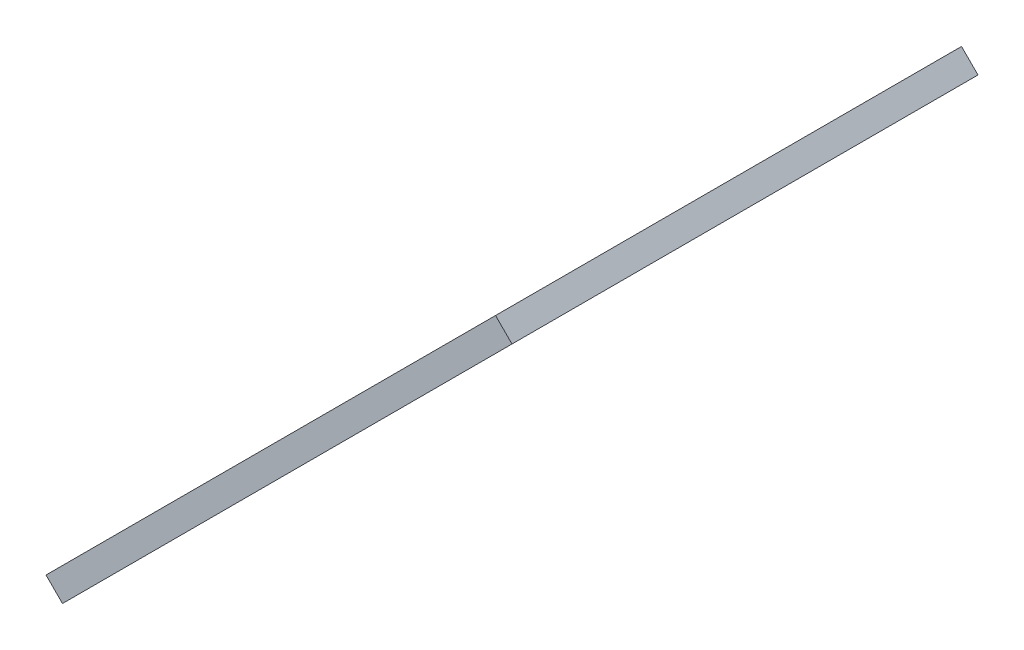
SolidWorks part; units mm, degrees
ref_plane "Front Plane" through (0, 0, 0) normal (0, 0, 1) x (1, 0, 0)
ref_plane "Top Plane" through (0, 0, 0) normal (0, 1, 0) x (1, 0, 0)
ref_plane "Right Plane" through (0, 0, 0) normal (1, 0, 0) x (0, 0, -1)
sketch "Sketch1" plane through (0, 0, 0) normal (0, 0, 1) x (1, 0, 0)
  line L0 (0, 127) -> (4.4901, 122.5099)
  line L1 (0, 127) -> (-122.5099, 4.4901)
  line L2 (4.4901, 122.5099) -> (-118.0197, 0)
  line L3 (-122.5099, 4.4901) -> (-118.0197, 0)
  line L4 (127, 0) -> (0, 127) construction
  line L5 (4.4901, -122.5099) -> (-122.5099, 4.4901) construction
  dimension "D1" = 6.35
extrude "Boss-Extrude1" add sketch "Sketch1" along normal up to surface (127 mm away)
